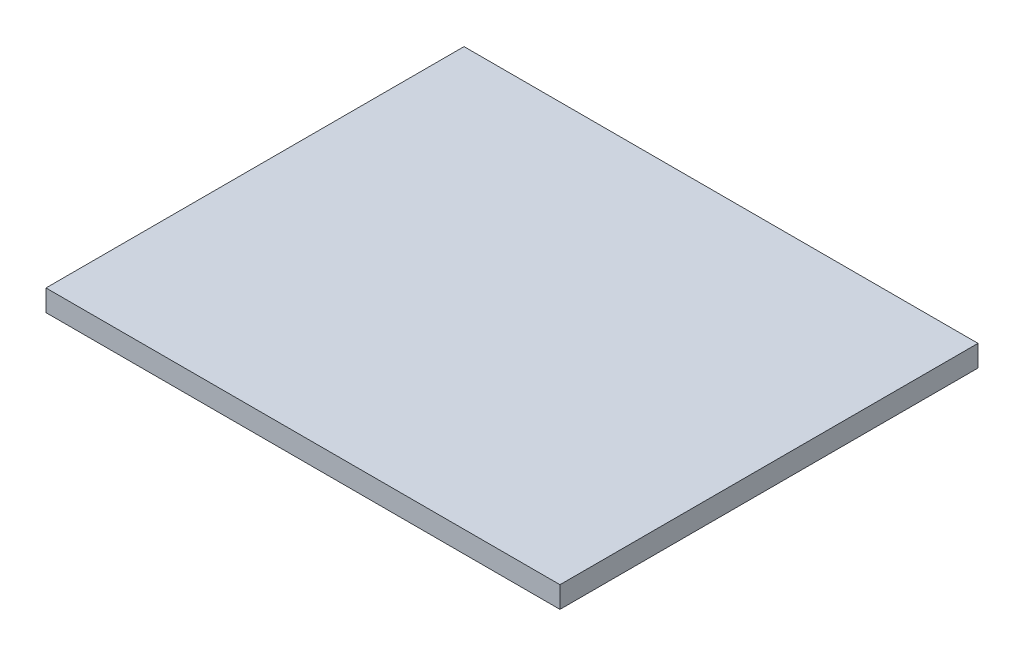
SolidWorks part; units mm, degrees
ref_plane "Front Plane" through (0, 0, 0) normal (0, 0, 1) x (1, 0, 0)
ref_plane "Top Plane" through (0, 0, 0) normal (0, 1, 0) x (1, 0, 0)
ref_plane "Right Plane" through (0, 0, 0) normal (1, 0, 0) x (0, 0, -1)
sketch "Sketch1" plane through (0, 0, 0) normal (0, 1, 0) x (1, 0, 0)
  line L1 (-65.9453, 79.2259) -> (86.4547, 79.2259)
  line L2 (-65.9453, 79.2259) -> (-65.9453, -44.7261)
  line L3 (-65.9453, -44.7261) -> (86.4547, -44.7261)
  line L4 (86.4547, 79.2259) -> (86.4547, -44.7261)
  dimension "D1" = 152.4
  dimension "D2" = 123.952
extrude "Boss-Extrude1" add sketch "Sketch1" along normal blind 6.35
